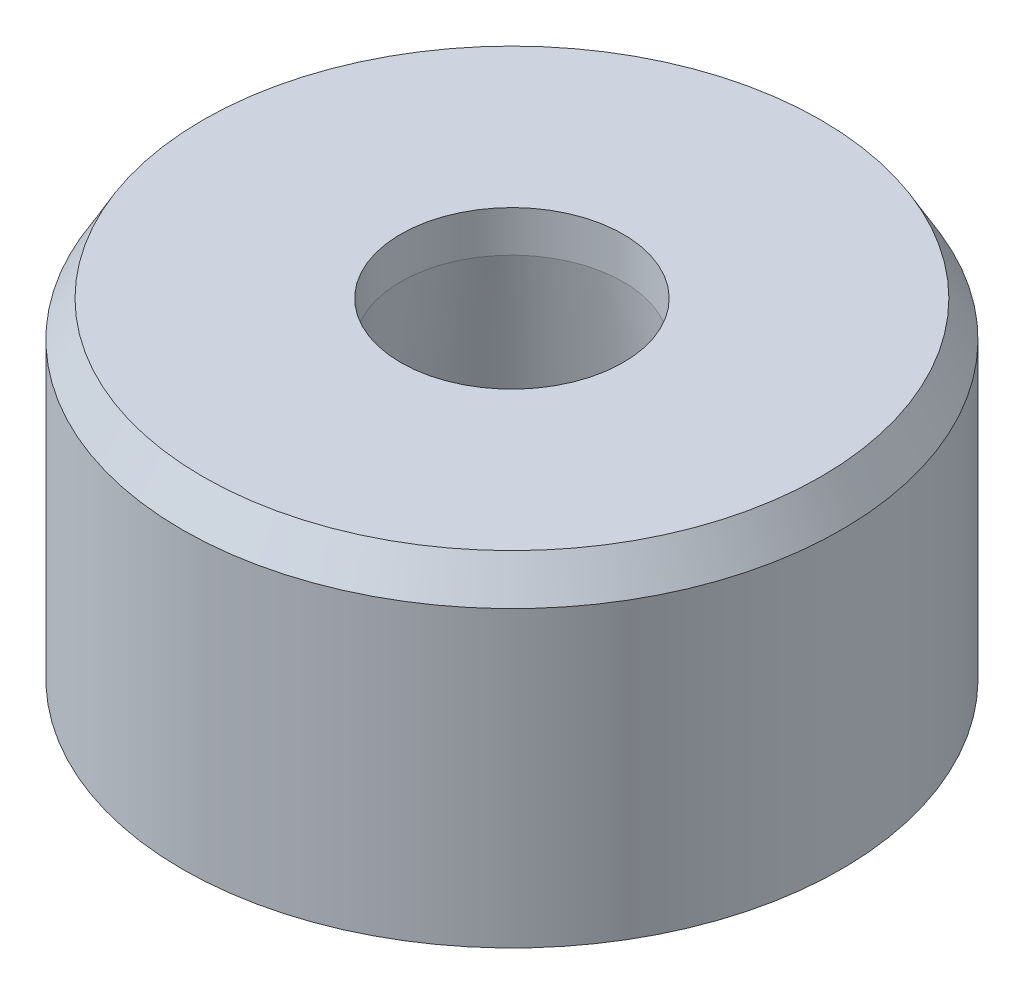
SolidWorks part; units mm, degrees
ref_plane "Front" through (0, 0, 0) normal (0, 0, 1) x (1, 0, 0)
ref_plane "Top" through (0, 0, 0) normal (0, 1, 0) x (1, 0, 0)
ref_plane "Right" through (0, 0, 0) normal (1, 0, 0) x (0, 0, -1)
sketch "Sketch1" plane through (0, 0, 0) normal (0, 1, 0) x (1, 0, 0)
  circle A0 centre (0, 0) radius 2.7
  circle A1 centre (0, 0) radius 8
  dimension "D1" = 5.4
  dimension "D2" = 16
extrude "Boss-Extrude1" add sketch "Sketch1" along normal blind 8
chamfer "Chamfer1" distance 7 angle 8 1 edges at (0, 0, 2.7) first distance on face at (0, 8, 2.7)
chamfer "Chamfer2" distance 0.5 angle 60 1 edges at (0, 8, 8) first distance on face at (0, 8, 8)
equation "\"height\"= 13 - 5"
equation "\"D1@Boss-Extrude1\"=\"height\""
